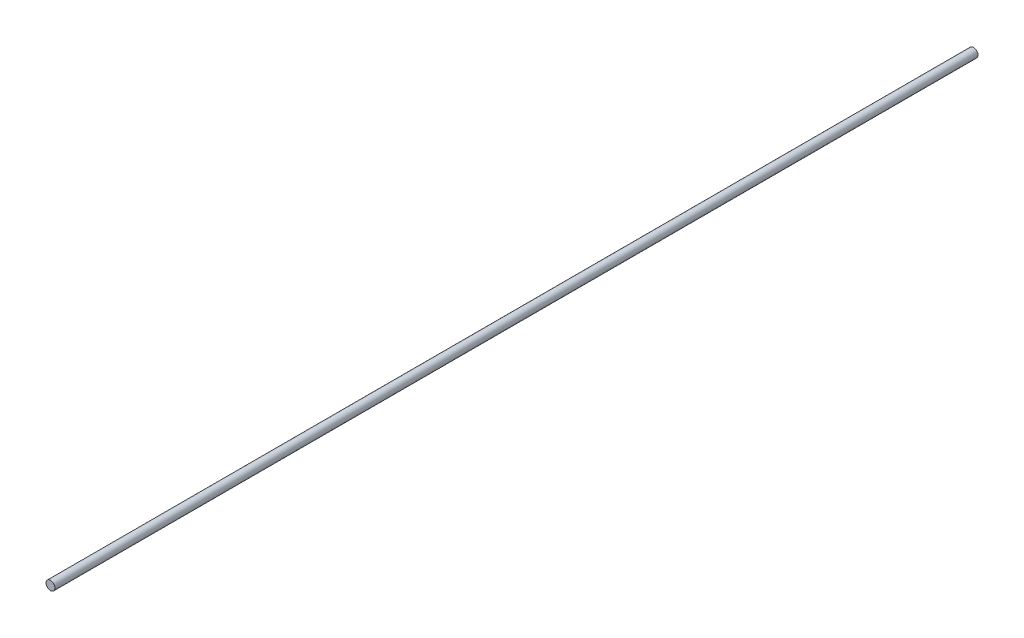
SolidWorks part; units mm, degrees
material "AISI 1020"
ref_plane "Front Plane" through (0, 0, 0) normal (0, 0, 1) x (1, 0, 0)
ref_plane "Top Plane" through (0, 0, 0) normal (0, 1, 0) x (1, 0, 0)
ref_plane "Right Plane" through (0, 0, 0) normal (1, 0, 0) x (0, 0, -1)
sketch "Sketch1" plane through (0, 0, 0) normal (0, 0, 1) x (1, 0, 0)
  circle A0 centre (0, 0) radius 7.9375
  dimension "D1" = 15.875
extrude "Boss-Extrude1" add sketch "Sketch1" along normal blind 2254.25
sketch "Sketch2" plane through (0, 0, 0) normal (0, 0, -1) x (-1, 0, 0)
  circle A0 centre (0, 0) radius 7.9375
extrude "Cut-Extrude1" cut sketch "Sketch2" against normal blind 539.75
sketch "Sketch3" plane through (0, 0, 2254.25) normal (0, 0, 1) x (1, 0, 0)
  circle A0 centre (0, 0) radius 7.9375
extrude "Cut-Extrude2" cut sketch "Sketch3" against normal blind 69.85
